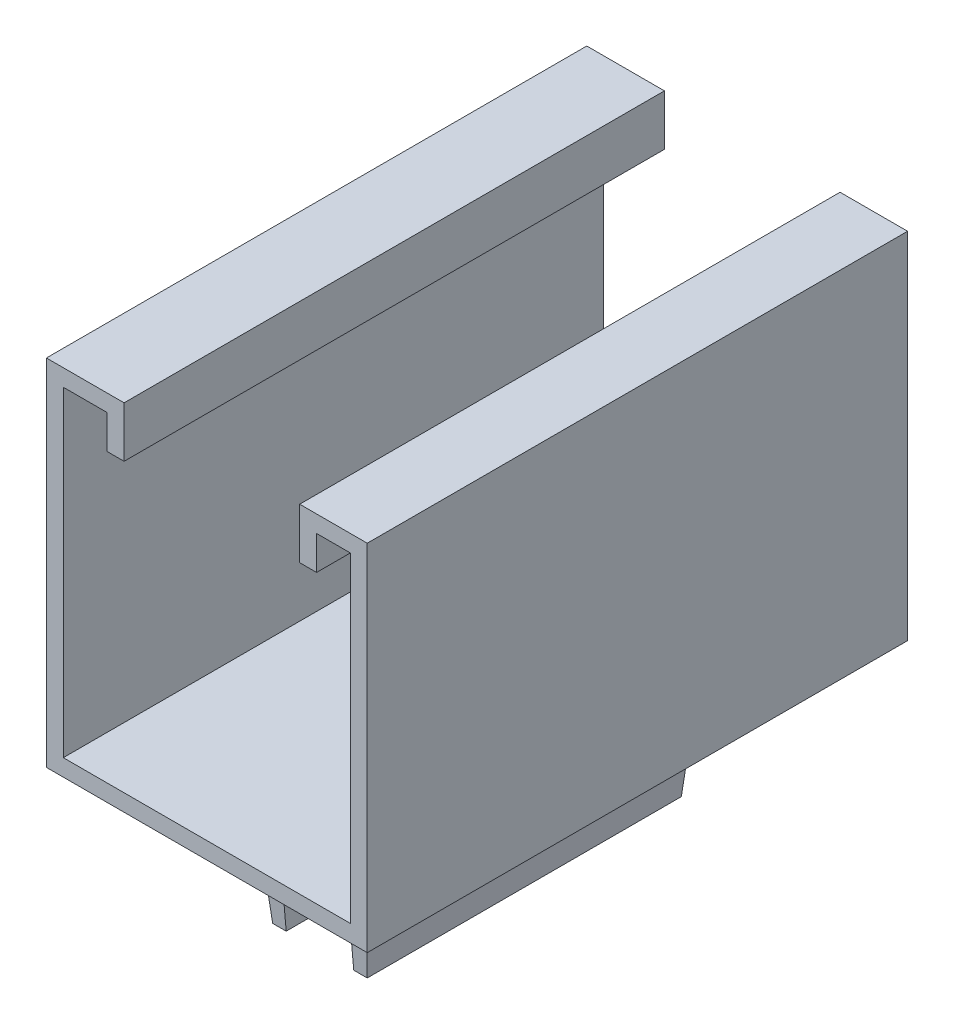
SolidWorks part; units mm, degrees
material "1060 Alloy"
ref_plane "Front Plane" through (0, 0, 0) normal (0, 0, 1) x (1, 0, 0)
ref_plane "Top Plane" through (0, 0, 0) normal (0, 1, 0) x (1, 0, 0)
ref_plane "Right Plane" through (0, 0, 0) normal (1, 0, 0) x (0, 0, -1)
sketch "Sketch1" plane through (0, 0, 0) normal (0, 0, 1) x (1, 0, 0)
  line L0 (0, 0) -> (0, -60.325)
  line L1 (0, -60.325) -> (53.975, -60.325)
  line L2 (53.975, -60.325) -> (53.975, 0)
  line L3 (53.975, 0) -> (47.625, 0)
  line L4 (47.625, 0) -> (47.625, -6.35)
  line L5 (11.43, 3.175) -> (11.43, -6.35)
  line L6 (0, 0) -> (8.255, 0)
  line L7 (8.255, 0) -> (8.255, -6.35)
  line L8 (-3.175, 3.175) -> (11.43, 3.175)
  line L9 (-3.175, 3.175) -> (-3.175, -63.5)
  line L10 (-3.175, -63.5) -> (57.15, -63.5)
  line L11 (57.15, -63.5) -> (57.15, 3.175)
  line L12 (57.15, 3.175) -> (44.45, 3.175)
  line L13 (44.45, 3.175) -> (44.45, -6.35)
  line L14 (8.255, -6.35) -> (11.43, -6.35)
  line L15 (44.45, -6.35) -> (47.625, -6.35)
  dimension "D1" = 53.975
  dimension "D2" = 60.325
  dimension "D3" = 6.35
  dimension "D4" = 39.37
  dimension "D5" = 6.35
  dimension "D6" = 3.175
extrude "Boss-Extrude1" add sketch "Sketch1" along normal blind 101.6
sketch "Sketch2" plane through (0, -63.5, 0) normal (0, -1, 0) x (-1, 0, 0)
  line L0 (-15.875, -82.55) -> (-15.875, -19.05)
  line L1 (3.175, -101.6) -> (-57.15, -101.6)
  line L2 (3.175, -101.6) -> (3.175, 0)
  line L3 (3.175, 0) -> (-57.15, 0)
  line L4 (-57.15, -101.6) -> (-57.15, 0)
  line L5 (-15.875, -19.05) -> (-38.1, -19.05)
  line L6 (-38.1, -82.55) -> (-38.1, -19.05)
  line L7 (-15.875, -82.55) -> (-38.1, -82.55)
  line L8 (-26.9875, -19.05) -> (-26.9875, -82.55) construction
  line L10 (-33.3375, -82.55) -> (-20.6375, -82.55)
  line L11 (-33.3375, -82.55) -> (-33.3375, -19.05)
  line L12 (-33.3375, -19.05) -> (-20.6375, -19.05)
  line L13 (-20.6375, -82.55) -> (-20.6375, -19.05)
  line L14 (-33.3375, -82.55) -> (-20.6375, -19.05) construction
  line L15 (-33.3375, -19.05) -> (-20.6375, -82.55) construction
  point P12 (-26.9875, -50.8)
  dimension "D2" = 6.35
  dimension "D1" = 19.05
extrude "Boss-Extrude2" add sketch "Sketch2" along normal blind 25.4 draft 5 contours L0 L5 L6 L7
extrude "Cut-Extrude1" cut sketch "Sketch2<3>" along normal up to surface (25.4 mm away) contours L7 L13 L5 L11 region at (26.9875, -63.5, 50.8) up to face at (26.9875, -88.9, 50.8)
sketch "Sketch2<3>" plane through (0, -63.5, 0) normal (0, -1, 0) x (-1, 0, 0) same geometry as "Sketch2"
sketch "Sketch3" plane through (20.6375, 0, 0) normal (1, 0, 0) x (0, 0, -1)
  line L0 (-50.8, -88.9) -> (-50.8, -63.5) construction
  line L1 (-80.3278, -88.9) -> (-21.2722, -88.9) construction
  line L2 (-101.6, -63.5) -> (0, -63.5) construction
  line L3 (-50.8, -76.2) -> (-81.4389, -76.2) construction
  line L4 (-80.3278, -88.9) -> (-82.55, -63.5) construction
  line L5 (-50.8, -76.2) -> (-20.1611, -76.2) construction
  circle A0 centre (-66.1194, -76.2) radius 3.175
  circle A1 centre (-35.4806, -76.2) radius 3.175
  dimension "D1" = 6.35
extrude "Cut-Extrude2" cut sketch "Sketch3" along normal through all both and the other way through all
